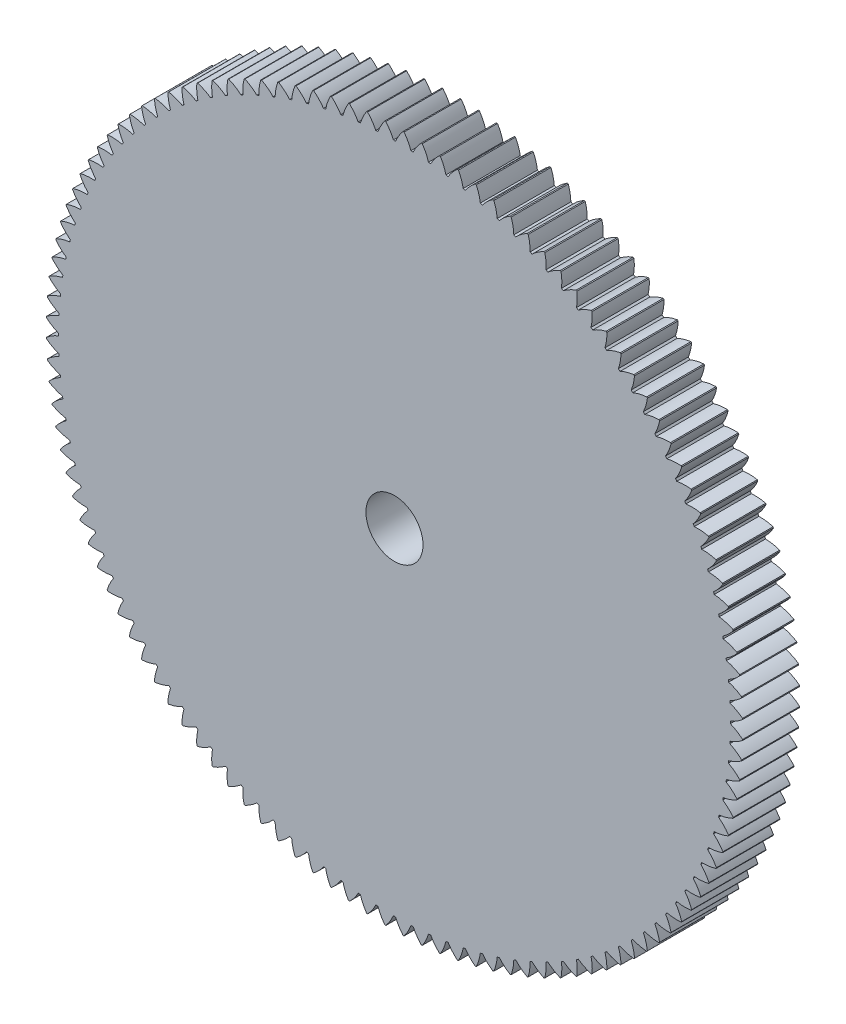
SolidWorks part; units mm, degrees
ref_plane "Plano frontal" through (0, 0, 0) normal (0, 0, 1) x (1, 0, 0)
ref_plane "Plano superior" through (0, 0, 0) normal (0, 1, 0) x (1, 0, 0)
ref_plane "Plano direito" through (0, 0, 0) normal (1, 0, 0) x (0, 0, -1)
sketch "Esboço1" plane through (0, 0, 0) normal (0, 0, 1) x (1, 0, 0)
  circle A0 centre (0, 0) radius 61
  dimension "D1" = 122
extrude "Ressalto-extrusão1" add sketch "Esboço1" along normal blind 10 contours A0
sketch "Esboço2" plane through (0, 0, 10) normal (0, 0, 1) x (1, 0, 0)
  line L0 (0, 0) -> (0, 56.38) construction
  line L1 (0, 0) -> (0.7854, 59.9949) construction
  circle A0 centre (0, 0) radius 60 construction
  circle A1 centre (0, 0) radius 56.38 construction
  arc A2 (0.1937, 58.8347) -> (-0.1937, 58.8347) centre (0, 0) ccw
  arc A3 (1.5109, 60.9813) -> (-1.5109, 60.9813) centre (0, 0) ccw
  arc A4 (0.7854, 59.9949) -> (1.5109, 60.9813) centre (7.3961, 55.8928) cw
  arc A5 (0.7854, 59.9949) -> (0.1937, 58.8347) centre (7.3961, 55.8928) ccw
  arc A6 (-0.7854, 59.9949) -> (-0.1937, 58.8347) centre (-7.3961, 55.8928) cw
  arc A7 (-0.7854, 59.9949) -> (-1.5109, 60.9813) centre (-7.3961, 55.8928) ccw
  dimension "D1" = 120
  dimension "D2" = 112.76
  dimension "D3" = 117.67
  dimension "D5" = 122
  dimension "D6" = 7.78
  dimension "D7" = 7.78
  dimension "D4" = 0.75
extrude "Corte-extrusão1" cut sketch "Esboço2" against normal blind 10
pattern_circular "PadrãoCircular2" count 120 over 360 about axis through (0, 0, 10) along (0, 0, 1) of "Corte-extrusão1"
sketch "Esboço3" plane through (0, 0, 10) normal (0, 0, 1) x (1, 0, 0)
  circle A0 centre (0, 0) radius 5
  dimension "D1" = 10
extrude "Corte-extrusão2" cut sketch "Esboço3" against normal blind 10
